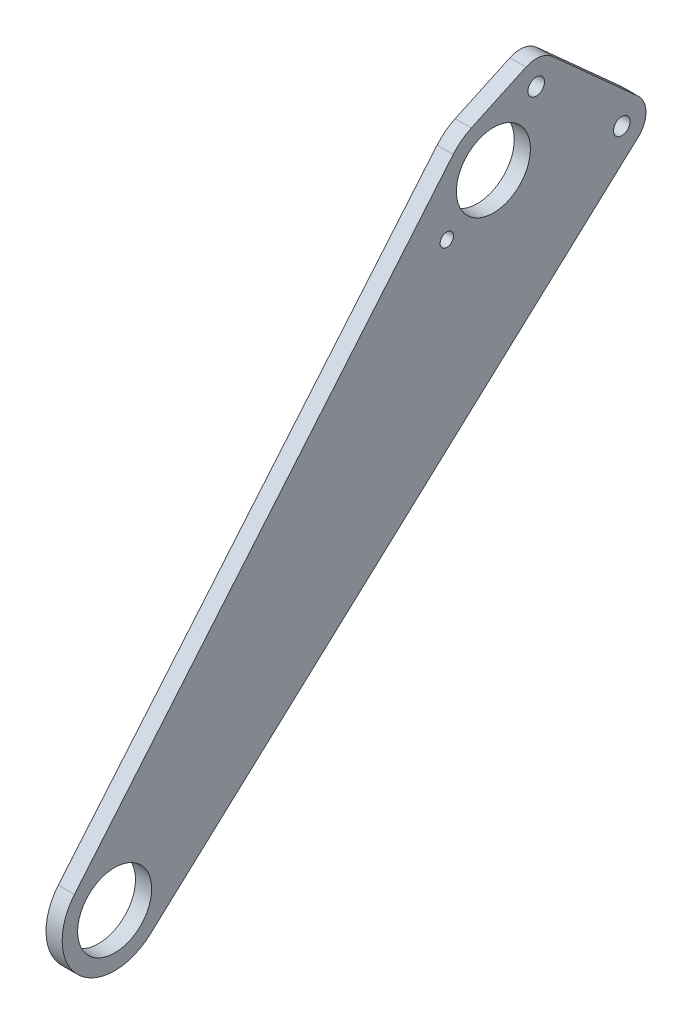
SolidWorks part; units mm, degrees
material "6061-T6 (SS)"
ref_plane "Front Plane" through (0, 0, 0) normal (0, 0, 1) x (1, 0, 0)
ref_plane "Top Plane" through (0, 0, 0) normal (0, 1, 0) x (1, 0, 0)
ref_plane "Right Plane" through (0, 0, 0) normal (1, 0, 0) x (0, 0, -1)
sketch "Sketch1" plane through (0, 0, 0) normal (1, 0, 0) x (0, 0, -1)
  line L0 (0, 0) -> (47.4141, 0) construction
  line L1 (0, 0) -> (143.6841, 143.6841) construction
  line L2 (143.6841, 143.6841) -> (148.964, 177.5652) construction
  line L3 (0, 0) -> (148.964, 177.5652) construction
  line L4 (0, 0) -> (199.4397, 167.3498) construction
  line L5 (148.964, 177.5652) -> (165.7989, 197.6325) construction
  line L6 (-15.8106, 13.2639) -> (133.1534, 190.8291)
  line L7 (140.2738, 196.2838) -> (161.7881, 206.2718)
  line L8 (172.1715, 204.7117) -> (205.8123, 174.429)
  line L9 (205.8681, 160.3212) -> (13.9282, -15.2286)
  line L10 (146.324, 160.6246) -> (130.6383, 163.069) construction
  circle A0 centre (0, 0) radius 14.5542
  circle A1 centre (143.6841, 143.6841) radius 14.5542 construction
  circle A2 centre (148.964, 177.5652) radius 14.5542
  circle A3 centre (199.4397, 167.3498) radius 3.2639
  circle A4 centre (165.7989, 197.6325) radius 3.2639
  arc A5 (172.1715, 204.7117) -> (161.7881, 206.2718) centre (165.7989, 197.6325) ccw
  arc A6 (205.8681, 160.3212) -> (205.8123, 174.429) centre (199.4397, 167.3498) ccw
  arc A7 (140.2738, 196.2838) -> (133.1534, 190.8291) centre (148.964, 177.5652) ccw
  arc A8 (13.9282, -15.2286) -> (-15.8106, 13.2639) centre (0, 0) cw
  circle A9 centre (130.6383, 163.069) radius 2.6289
  dimension "D1" = 29.1084
  dimension "D4" = 34.29
  dimension "D5" = 29.1084
  dimension "D6" = 29.1084
  dimension "D10" = 6.5278
  dimension "D12" = 6.5278
  dimension "D13" = 9.525
  dimension "D14" = 9.525
  dimension "D15" = 20.6375
  dimension "D16" = 20.6375
  dimension "D18" = 5.2578
  dimension "D2" = 45
  dimension "D3" = 203.2
  dimension "D7" = 231.775
  dimension "D8" = 260.35
  dimension "D9" = 40
  dimension "D11" = 26.1937
  dimension "D17" = 15.875
extrude "Boss-Extrude1" add sketch "Sketch1" along normal blind 6.35
sketch3d "3DSketch1"
  point P0 (3.175, 93.26, 20.6375)
